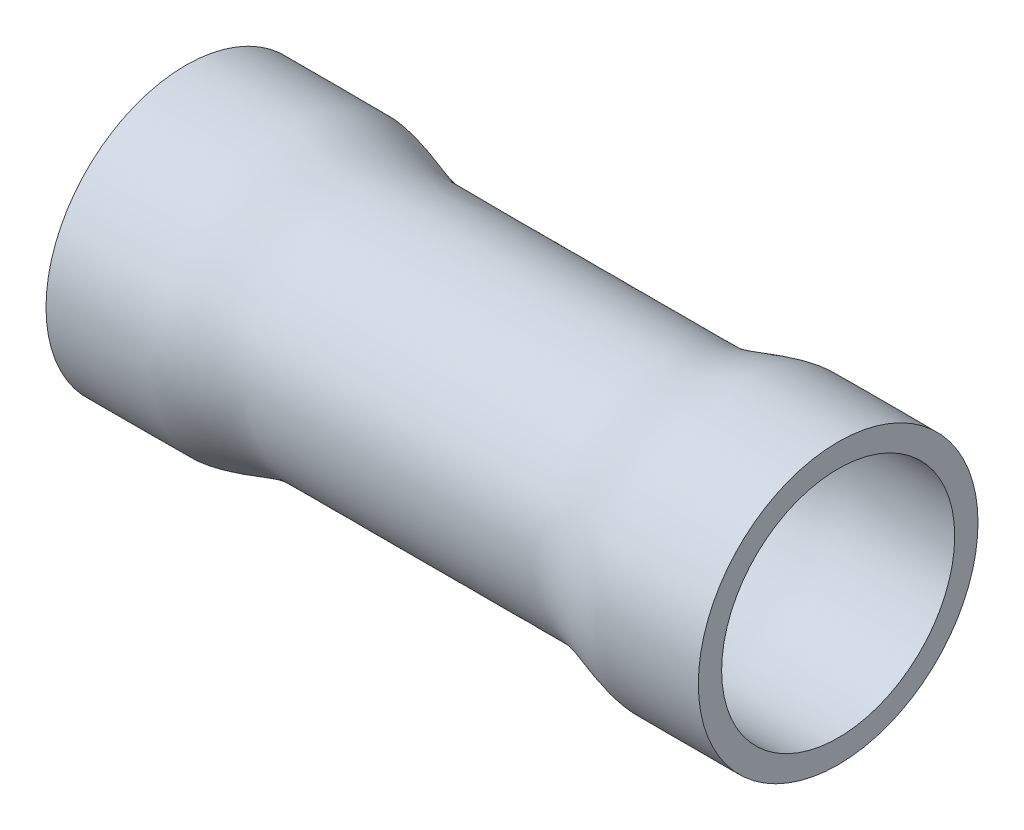
SolidWorks part; units mm, degrees
ref_plane "Front Plane" through (0, 0, 0) normal (0, 0, 1) x (1, 0, 0)
ref_plane "Top Plane" through (0, 0, 0) normal (0, 1, 0) x (1, 0, 0)
ref_plane "Right Plane" through (0, 0, 0) normal (1, 0, 0) x (0, 0, -1)
sketch "FilterSketch" plane through (0, 0, 0) normal (1, 0, 0) x (0, 0, -1)
  line L0 (-100, 0) -> (100, 0) construction
  circle A0 centre (0, 0) radius 1.5
  circle A1 centre (0, 0) radius 2
  dimension "InnerDiameter" = 3
  dimension "D3" = 0.5
extrude "Boss-Extrude1" add sketch "FilterSketch" along normal blind 3 and the other way blind 3
sketch "Sketch2" plane through (0, 0, 0) normal (0, 0, 1) x (1, 0, 0)
  line L0 (0, 2.6) -> (0, 1.4458) construction
  line L1 (0, 0) -> (0, -3.3878) construction
  line L2 (5, 2.1) -> (5, 0) construction
  line L3 (3, 2) -> (-3, 2) construction
  line L5 (4.9, 3.0012) -> (7, 3.0012) construction
  line L6 (-7, 2.5012) -> (-4.9, 2.5012) construction
  line L7 (-7, 3.0012) -> (-7, 2.5012)
  line L10 (-4.9, 3.0012) -> (-7, 3.0012) construction
  line L11 (-3, 2.6) -> (-3, 2.1) construction
  line L13 (-3, 2.6) -> (3, 2.6) construction
  line L15 (-12.5, 0) -> (0, 0) construction
  line L16 (3, 2.1) -> (7, 2.1) construction
  line L17 (-12.5, 0) -> (12.5, 0) construction
  line L18 (0, 0) -> (12.5, 0) construction
  line L19 (7, 3.0012) -> (7, 2.5012)
  line L20 (7, 2.5012) -> (4.9, 2.5012) construction
  line L21 (0.1, 0) -> (0.1, -3.9646) construction
  line L22 (3, -2) -> (3, 2) construction
  line L23 (4.9, 3.0012) -> (7, 3.0012) construction
  line L24 (7, 2.5012) -> (4.9, 2.5012) construction
  line L26 (3, 2.1) -> (-3, 2.1) construction
  arc A0 (0, 2.6) -> (3, 2.6) centre (1.5, 470.5041) ccw construction
  spline S0 degree 3 poles (4.9, 3.0012) (4.5158, 3.0012) (3.3464, 2.6011) (3, 2.6) knots 0 0 0 0 1 1 1 1 construction
  spline S1 degree 3 poles (-3, 2.1) (-3.6473, 2.1) (-4.2253, 2.5012) (-4.9, 2.5012) knots 0 0 0 0 1 1 1 1 construction
  spline S2 degree 3 poles (4.9, 2.5012) (4.5131, 2.5012) (3.4494, 2.1) (3, 2.1) knots 0 0 0 0 1 1 1 1 construction
  spline S3 degree 3 poles (-3, 2.6) (-3.6473, 2.6) (-4.2253, 3.0012) (-4.9, 3.0012) knots 0 0 0 0 1 1 1 1 construction
  spline S4 degree 3 poles (-7, 3.0012) (-6.475, 3.0012) (-5.95, 3.0012) (-5.425, 3.0012) (-5.3654, 3.0012) (-5.2461, 3.0012) (-5.0672, 3.0012) (-4.9479, 3.0012) (-4.8883, 3.0012) (-4.8548, 3.0012) (-4.7878, 3.0012) (-4.6869, 2.9924) (-4.6209, 2.9809) (-4.5879, 2.9751) (-4.568, 2.9717) (-4.5281, 2.9647) (-4.4687, 2.9521) (-4.4292, 2.9432) (-4.4095, 2.9385) (-4.0912, 2.8633) (-3.7866, 2.7379) (-3.4751, 2.6627) (-3.4561, 2.6581) (-3.4181, 2.6493) (-3.3608, 2.6368) (-3.3224, 2.6299) (-3.3032, 2.6264) (-3.2711, 2.6205) (-3.2067, 2.6089) (-3.1082, 2.6) (-3.0428, 2.6) (-3.0101, 2.6) (-2.9557, 2.6) (-2.847, 2.6) (-2.6839, 2.6) (-2.5752, 2.6) (-2.5208, 2.6) (-0.8403, 2.6) (0.8403, 2.6) (2.5208, 2.6) (2.5752, 2.6) (2.6839, 2.6) (2.847, 2.6) (2.9557, 2.6) (3.0101, 2.6) (3.0428, 2.6) (3.1082, 2.6) (3.2067, 2.6089) (3.2711, 2.6205) (3.3032, 2.6264) (3.3224, 2.6299) (3.3608, 2.6368) (3.4181, 2.6493) (3.4561, 2.6581) (3.4751, 2.6627) (3.7866, 2.7379) (4.0912, 2.8633) (4.4095, 2.9385) (4.4292, 2.9432) (4.4687, 2.9521) (4.5281, 2.9647) (4.568, 2.9717) (4.5879, 2.9751) (4.6209, 2.9809) (4.6869, 2.9924) (4.7878, 3.0012) (4.8548, 3.0012) (4.8883, 3.0012) (4.9479, 3.0012) (5.0672, 3.0012) (5.2461, 3.0012) (5.3654, 3.0012) (5.425, 3.0012) (5.95, 3.0012) (6.475, 3.0012) (7, 3.0012) knots 0 0 0 0 0.110465 0.110465 0.110465 0.123013 0.135561 0.148109 0.148109 0.148109 0.155157 0.162206 0.169254 0.169254 0.169254 0.173511 0.177769 0.182026 0.182026 0.182026 0.250856 0.250856 0.250856 0.255047 0.259239 0.26343 0.26343 0.26343 0.270454 0.277478 0.284502 0.284502 0.284502 0.296178 0.307855 0.319531 0.319531 0.319531 0.680469 0.680469 0.680469 0.692145 0.703822 0.715498 0.715498 0.715498 0.722522 0.729546 0.73657 0.73657 0.73657 0.740761 0.744953 0.749144 0.749144 0.749144 0.817974 0.817974 0.817974 0.822231 0.826489 0.830746 0.830746 0.830746 0.837794 0.844843 0.851891 0.851891 0.851891 0.864439 0.876987 0.889535 0.889535 0.889535 1 1 1 1
  spline S5 degree 3 poles (-7, 2.5012) (-6.475, 2.5012) (-5.95, 2.5012) (-5.425, 2.5012) (-5.3654, 2.5012) (-5.2461, 2.5012) (-5.0672, 2.5012) (-4.9479, 2.5012) (-4.8883, 2.5012) (-4.8548, 2.5012) (-4.7878, 2.5012) (-4.6869, 2.4924) (-4.6209, 2.4809) (-4.5879, 2.4751) (-4.568, 2.4717) (-4.5281, 2.4647) (-4.4687, 2.4521) (-4.4292, 2.4432) (-4.4095, 2.4385) (-4.0912, 2.3633) (-3.7866, 2.2379) (-3.4751, 2.1627) (-3.4561, 2.1581) (-3.4181, 2.1493) (-3.3608, 2.1368) (-3.3224, 2.1299) (-3.3032, 2.1264) (-3.2711, 2.1205) (-3.2067, 2.1089) (-3.1082, 2.1) (-3.0428, 2.1) (-3.0101, 2.1) (-2.9557, 2.1) (-2.847, 2.1) (-2.6839, 2.1) (-2.5752, 2.1) (-2.5208, 2.1) (-0.8403, 2.1) (0.8403, 2.1) (2.5208, 2.1) (2.5752, 2.1) (2.6839, 2.1) (2.847, 2.1) (2.9557, 2.1) (3.0101, 2.1) (3.0428, 2.1) (3.1082, 2.1) (3.2067, 2.1089) (3.2711, 2.1205) (3.3032, 2.1264) (3.3224, 2.1299) (3.3608, 2.1368) (3.4181, 2.1493) (3.4561, 2.1581) (3.4751, 2.1627) (3.7866, 2.2379) (4.0912, 2.3633) (4.4095, 2.4385) (4.4292, 2.4432) (4.4687, 2.4521) (4.5281, 2.4647) (4.568, 2.4717) (4.5879, 2.4751) (4.6209, 2.4809) (4.6869, 2.4924) (4.7878, 2.5012) (4.8548, 2.5012) (4.8883, 2.5012) (4.9479, 2.5012) (5.0672, 2.5012) (5.2461, 2.5012) (5.3654, 2.5012) (5.425, 2.5012) (5.95, 2.5012) (6.475, 2.5012) (7, 2.5012) knots 0 0 0 0 0.110465 0.110465 0.110465 0.123013 0.135561 0.148109 0.148109 0.148109 0.155157 0.162206 0.169254 0.169254 0.169254 0.173511 0.177769 0.182026 0.182026 0.182026 0.250856 0.250856 0.250856 0.255047 0.259239 0.26343 0.26343 0.26343 0.270454 0.277478 0.284502 0.284502 0.284502 0.296178 0.307855 0.319531 0.319531 0.319531 0.680469 0.680469 0.680469 0.692145 0.703822 0.715498 0.715498 0.715498 0.722522 0.729546 0.73657 0.73657 0.73657 0.740761 0.744953 0.749144 0.749144 0.749144 0.817974 0.817974 0.817974 0.822231 0.826489 0.830746 0.830746 0.830746 0.837794 0.844843 0.851891 0.851891 0.851891 0.864439 0.876987 0.889535 0.889535 0.889535 1 1 1 1
  spline S6 degree 3 poles (3, 2.6) (3.6473, 2.6) (4.2253, 3.0012) (4.9, 3.0012) knots 0 0 0 0 1 1 1 1 construction
  spline S7 degree 3 poles (3, 2.1) (3.6473, 2.1) (4.2253, 2.5012) (4.9, 2.5012) knots 0 0 0 0 1 1 1 1 construction
  point P20 (0, 2.1)
  point P21 (0, 2.1)
  dimension "D2" = 0.1
  dimension "D4" = 0.4012
  dimension "D1" = 0.1
  dimension "D3" = 0.5
revolve "Revolve1" add sketch "Sketch2" angle 360 about L15
sketch "Sketch3" plane through (0, 0, 0) normal (0, 0, 1) x (1, 0, 0)
  point P0 (0, 0)
other "CPoint1" parameters "Diameter"=3, "StubLength"=1
ref_axis "Axis1" through (10, 0, 0) along (-1, 0, 0)
